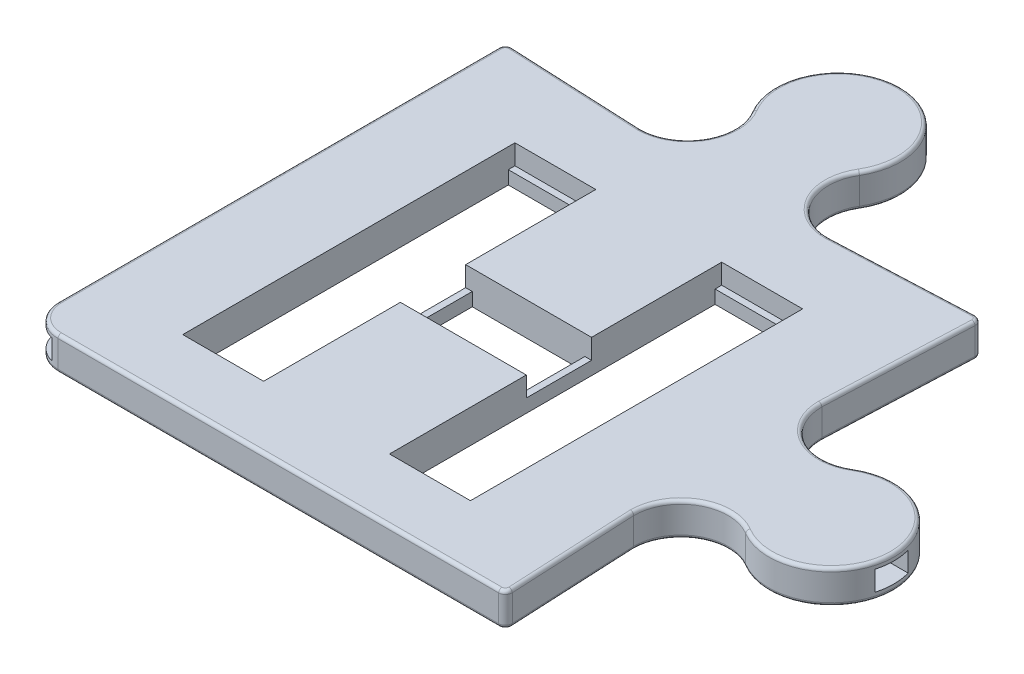
SolidWorks part; units mm, degrees
ref_plane "Front Plane" through (0, 0, 0) normal (0, 0, 1) x (1, 0, 0)
ref_plane "Top Plane" through (0, 0, 0) normal (0, 1, 0) x (1, 0, 0)
ref_plane "Right Plane" through (0, 0, 0) normal (1, 0, 0) x (0, 0, -1)
sketch "Sketch1" plane through (0, 0, 0) normal (0, 1, 0) x (1, 0, 0)
  line L0 (-31, -36) -> (37, -36) construction
  line L1 (-36, 37) -> (-36, -31) construction
  line L2 (-14.1421, 36) -> (-36, 37) construction
  line L3 (37, 37) -> (14.1421, 36) construction
  line L4 (36, 13.1421) -> (37, 37) construction
  line L5 (37, -36) -> (36, -15.1421) construction
  line L6 (-35.4, 36.3719) -> (-35.4, -31)
  line L7 (-36, 36) -> (36, 36) construction
  line L8 (-36, 36) -> (-36, -36) construction
  line L9 (-36, -36) -> (36, -36) construction
  line L10 (36, 36) -> (36, -36) construction
  line L11 (-31, -35.4) -> (36.3705, -35.4)
  line L12 (36.3705, -35.4) -> (35.4, -15.1568)
  line L13 (35.4, 13.155) -> (36.3732, 36.372)
  line L14 (36.3732, 36.372) -> (14.1555, 35.4)
  line L15 (-14.1562, 35.4) -> (-35.4, 36.3719)
  line L16 (-30, -24) -> (30, -24) construction
  line L17 (-30, 29) -> (30, 29) construction
  line L18 (-30, 29) -> (-30, -31) construction
  line L19 (-30, -31) -> (30, -31) construction
  line L20 (30, 29) -> (30, -31) construction
  line L21 (-30, 24) -> (30, 24) construction
  line L22 (-30, 24) -> (-30, -26) construction
  line L23 (-30, -26) -> (30, -26) construction
  line L24 (30, 24) -> (30, -26) construction
  arc A0 (-36, -31) -> (-31, -36) centre (-31, -31) ccw construction
  arc A1 (-14.1421, 36) -> (-8.571, 45.8485) centre (-14.1421, 42.5) ccw construction
  arc A2 (8.571, 45.8485) -> (-8.571, 45.8485) centre (0, 51) ccw construction
  arc A3 (8.571, 45.8485) -> (14.1421, 36) centre (14.1421, 42.5) ccw construction
  arc A4 (36, 13.1421) -> (45.8485, 7.571) centre (42.5, 13.1421) ccw construction
  arc A5 (45.8485, -9.571) -> (45.8485, 7.571) centre (51, -1) ccw construction
  arc A6 (45.8485, -9.571) -> (36, -15.1421) centre (42.5, -15.1421) ccw construction
  arc A7 (-35.4, -31) -> (-31, -35.4) centre (-31, -31) ccw
  arc A8 (46.1576, -9.0567) -> (35.4, -15.1568) centre (42.5, -15.1421) ccw
  arc A9 (46.1576, -9.0567) -> (46.1576, 7.0567) centre (51, -1) ccw
  arc A10 (35.4, 13.155) -> (46.1576, 7.0567) centre (42.5, 13.1421) ccw
  arc A11 (8.0567, 46.1576) -> (14.1555, 35.4) centre (14.1421, 42.5) ccw
  arc A12 (8.0567, 46.1576) -> (-8.0567, 46.1576) centre (0, 51) ccw
  arc A13 (-14.1562, 35.4) -> (-8.0567, 46.1576) centre (-14.1421, 42.5) ccw
  point P32 (36, 0)
  point P34 (0, 36)
  dimension "D5" = 6.5
  dimension "D6" = 10
  dimension "D7" = 6.5
  dimension "D13" = 5
  dimension "D9" = 10
  dimension "D11" = 6.5
  dimension "D12" = 6.5
  dimension "D1" = 72
  dimension "D2" = 1
  dimension "D3" = 1
  dimension "D4" = 15
  dimension "D8" = 1
  dimension "D10" = 35
  dimension "D14" = 15
  dimension "D15" = 36
  dimension "D16" = 1
  dimension "D18" = 60
  dimension "D19" = 60
  dimension "D20" = 5
  dimension "D21" = 6
  dimension "D22" = 5
  dimension "D23" = 50
  dimension "D24" = 2
  dimension "D17" = 0.6
extrude "Boss-Extrude1" add sketch "Sketch1" along normal blind 5
sketch "Sketch6" plane through (0, 0, 0) normal (0, -1, 0) x (1, 0, 0)
  line L0 (-35.4, -36.3719) -> (-35.4, 31) construction
  line L1 (-35.4, 17.9) -> (-27.4, 17.9)
  line L2 (-35.4, 17.9) -> (-35.4, -16.1)
  line L3 (-35.4, -16.1) -> (-27.4, -16.1)
  line L4 (-27.4, 17.9) -> (-27.4, -16.1)
  line L5 (-31, 35.4) -> (36.3705, 35.4) construction
  line L6 (-35.4, 14.65) -> (-30.4, 14.65)
  line L7 (-35.4, 14.65) -> (-35.4, -12.85)
  line L8 (-35.4, -12.85) -> (-30.4, -12.85)
  line L9 (-30.4, 14.65) -> (-30.4, -12.85)
  point P15 (-27.4, 0.9)
  point P16 (-30.4, 0.9)
  line M28 (-35.4, 31) -> (-35.4, -36.3719)
  dimension "D1" = 8
  dimension "D2" = 20.75
  dimension "D3" = 27.5
  dimension "D4" = 5
  dimension "D5" = 34
extrude "Cut-Extrude3" cut sketch "Sketch6" against normal blind 3 from offset 1 contours L6 L9 L8 L3 L4 L1 M28 | L9 L6 L2 L8 region at (-29.8665, 0, 0.9) region at (-32.9, 0, 0.9) offset against normal yes
extrude "Cut-Extrude4" cut sketch "Sketch6<3>" against normal up to next contours L9 L6 L2 L8 region at (-32.9, 0, 0.9)
sketch "Sketch6<3>" plane through (0, 0, 0) normal (0, -1, 0) x (1, 0, 0) same geometry as "Sketch6"
sketch "Sketch8" plane through (0, 0, 0) normal (0, -1, 0) x (1, 0, 0)
  line L1 (-2.5, -51.4) -> (2.5, -51.4)
  line L2 (-2.5, -51.4) -> (-2.5, -60.4)
  line L3 (-2.5, -60.4) -> (2.5, -60.4)
  line L4 (2.5, -51.4) -> (2.5, -60.4)
  line L5 (51.4, 3.5) -> (60.4, 3.5)
  line L6 (51.4, 3.5) -> (51.4, -1.5)
  line L7 (51.4, -1.5) -> (60.4, -1.5)
  line L8 (60.4, 3.5) -> (60.4, -1.5)
  arc A0 (-8.0567, -46.1576) -> (8.0567, -46.1576) centre (0, -51) ccw construction
  arc A1 (46.1576, -7.0567) -> (46.1576, 9.0567) centre (51, 1) ccw construction
  point P4 (0, -60.4)
  point P13 (60.4, 1)
  dimension "D1" = 5
  dimension "D2" = 9
  dimension "D3" = 5
  dimension "D4" = 9
extrude "Cut-Extrude5" cut sketch "Sketch8" against normal blind 3 from offset 1 offset against normal yes
sketch "Sketch9" plane through (0, 0, 0) normal (0, -1, 0) x (1, 0, 0)
  line L0 (-31, 35.4) -> (36.3705, 35.4) construction
  line L1 (-35.4, 14.65) -> (-35.4, 31) construction
  line L2 (-31.7636, 35.3332) -> (-35.4, 31) construction
  line L3 (-33.2571, 29.735) -> (-30.0429, 33.565) construction
  line L4 (-30.0429, 33.565) -> (-33.2571, 29.735) construction
  line L5 (-30.0429, 33.565) -> (-32.7119, 35.8048)
  line L6 (-33.2571, 29.735) -> (-35.926, 31.9747)
  line L7 (-32.7119, 35.8048) -> (-35.926, 31.9747)
  circle A0 centre (-31.65, 31.65) radius 2.5
  arc A1 (-31, 35.4) -> (-35.4, 31) centre (-31, 31) ccw construction
  arc M41 (-31, 35.4) -> (-35.4, 31) centre (-31, 31) ccw
  dimension "D1" = 5
  dimension "D3" = 3.75
  dimension "D4" = 5.6569
  dimension "D2" = 3.75
extrude "Cut-Extrude6" cut sketch "Sketch9" against normal blind 3 from offset 1 contours A0 L5 L6 M41 | A0 L5 region at (-33.6239, 0, 33.3064) region at (-31.65, 0, 31.65) offset against normal yes
sketch "Sketch11" plane through (-35.4, 0, 0) normal (-1, 0, 0) x (0, 0, 1)
  line L0 (-13.155, 0) -> (-36.372, 0) construction
  line L1 (-25.1, 3) -> (-19.1, 3)
  line L2 (-25.1, 3) -> (-25.1, 1.5)
  line L3 (-25.1, 1.5) -> (-19.1, 1.5)
  line L4 (-19.1, 3) -> (-19.1, 1.5)
  line L5 (-16.1, 4) -> (-16.1, 1) construction
  line L6 (35.4, 0) -> (15.1568, 0) construction
  line L7 (20.9, 3) -> (26.9, 3)
  line L8 (20.9, 3) -> (20.9, 1.5)
  line L9 (20.9, 1.5) -> (26.9, 1.5)
  line L10 (26.9, 3) -> (26.9, 1.5)
  line L12 (17.9, 4) -> (17.9, 1) construction
  dimension "D1" = 3
  dimension "D2" = 1.5
  dimension "D3" = 3
  dimension "D4" = 6
  dimension "D5" = 3
  dimension "D6" = 1.5
  dimension "D7" = 6
  dimension "D8" = 3
fillet "Fillet1" radius 0.5 17 edges at (-35.4, 0, 22.825) (-34.1113, 0, 34.1113) (2.6853, 0, 35.4) (35.8853, 0, 25.2784) (38.9978, 0, 8.966) (60.4, 0, 1) (38.9986, 0, -6.9655) (35.8866, 0, -24.7635) (25.2643, 0, -35.886) (7.9657, 0, -38.9984) (0, 0, -60.4) (-7.9658, 0, -38.9981) (-24.7781, 0, -35.886) (-35.4, 0, -24.611) (-32.9, 0, -12.85) (-30.4, 0, 0.9) (-32.9, 0, 14.65)
fillet "Fillet2" radius 0.5 13 edges at (-7.9658, 5, -38.9981) (0, 5, -60.4) (7.9657, 5, -38.9984) (25.2643, 5, -35.886) (35.8866, 5, -24.7635) (38.9986, 5, -6.9655) (60.4, 5, 1) (38.9978, 5, 8.966) (35.8853, 5, 25.2784) (2.6853, 5, 35.4) (-34.1113, 5, 34.1113) (-35.4, 5, -2.686) (-24.7781, 5, -35.886)
fillet "Fillet3" radius 1 9 edges at (36.2202, 0.1464, -36.2187) (36.2202, 4.8536, -36.2187) (36.3732, 2.5, -36.372) (-35.2536, 0.1464, -36.2186) (-35.2536, 4.8536, -36.2186) (36.2169, 0.1464, 35.2536) (36.2169, 4.8536, 35.2536) (36.3705, 2.5, 35.4) (-35.4, 2.5, -36.3719)
extrude "Cut-Extrude9" cut sketch "Sketch11" against normal blind 3
chamfer "Chamfer1" distance 1 angle 50 2 edges at (-35.4, 1.5, 23.9) (-35.4, 1.5, -22.1) first distance on face at (-35.4, 2.25, -22.1)
sketch "Sketch12" plane through (0, 5, 0) normal (0, 1, 0) x (1, 0, 0)
  text T0 "H" font "Poppins" height 50
extrude "Cut-Extrude10" cut sketch "Sketch12" against normal through all
sketch "Sketch13" plane through (0, 0, 0) normal (0, -1, 0) x (1, 0, 0)
  line L0 (-9.46, 5.4106) -> (-9.46, 26) construction
  line L1 (-21.6303, 26) -> (-9.46, 26)
  line L2 (-21.6303, 26) -> (-21.6303, 25)
  line L3 (-21.6303, 25) -> (-9.46, 25)
  line L4 (-9.46, 26) -> (-9.46, 25)
  line L5 (21.6715, -24) -> (21.6715, 26) construction
  line L6 (9.4909, 26) -> (21.6715, 26)
  line L7 (9.4909, 26) -> (9.4909, 25)
  line L8 (9.4909, 25) -> (21.6715, 25)
  line L9 (21.6715, 26) -> (21.6715, 25)
  line L10 (-21.6303, 26) -> (-21.6303, -24) construction
  line L11 (-21.6303, -23) -> (-9.46, -23)
  line L12 (-21.6303, -23) -> (-21.6303, -24)
  line L13 (-21.6303, -24) -> (-9.46, -24)
  line L14 (-9.46, -23) -> (-9.46, -24)
  line L15 (-9.46, -24) -> (-9.46, -4.4101) construction
  line L16 (-21.6303, -24) -> (-9.46, -24) construction
  line L17 (9.4909, -4.4101) -> (9.4909, -24) construction
  line L18 (9.4909, -23) -> (21.6715, -23)
  line L19 (9.4909, -23) -> (9.4909, -24)
  line L20 (9.4909, -24) -> (21.6715, -24)
  line L21 (21.6715, -23) -> (21.6715, -24)
  line L22 (-9.46, -4.4101) -> (9.4909, -4.4101) construction
  line L23 (-9.46, 5.4106) -> (-8.46, 5.4106)
  line L24 (-9.46, 5.4106) -> (-9.46, -4.4101)
  line L25 (-9.46, -4.4101) -> (-8.46, -4.4101)
  line L26 (-8.46, 5.4106) -> (-8.46, -4.4101)
  line L28 (9.4909, 5.4106) -> (8.4909, 5.4106)
  line L29 (9.4909, 5.4106) -> (9.4909, -4.4101)
  line L30 (9.4909, -4.4101) -> (8.4909, -4.4101)
  line L31 (8.4909, 5.4106) -> (8.4909, -4.4101)
  dimension "D1" = 1
  dimension "D2" = 1
  dimension "D3" = 1
  dimension "D4" = 1
  dimension "D5" = 1
  dimension "D6" = 1
extrude "Boss-Extrude2" add sketch "Sketch13" against normal blind 2
